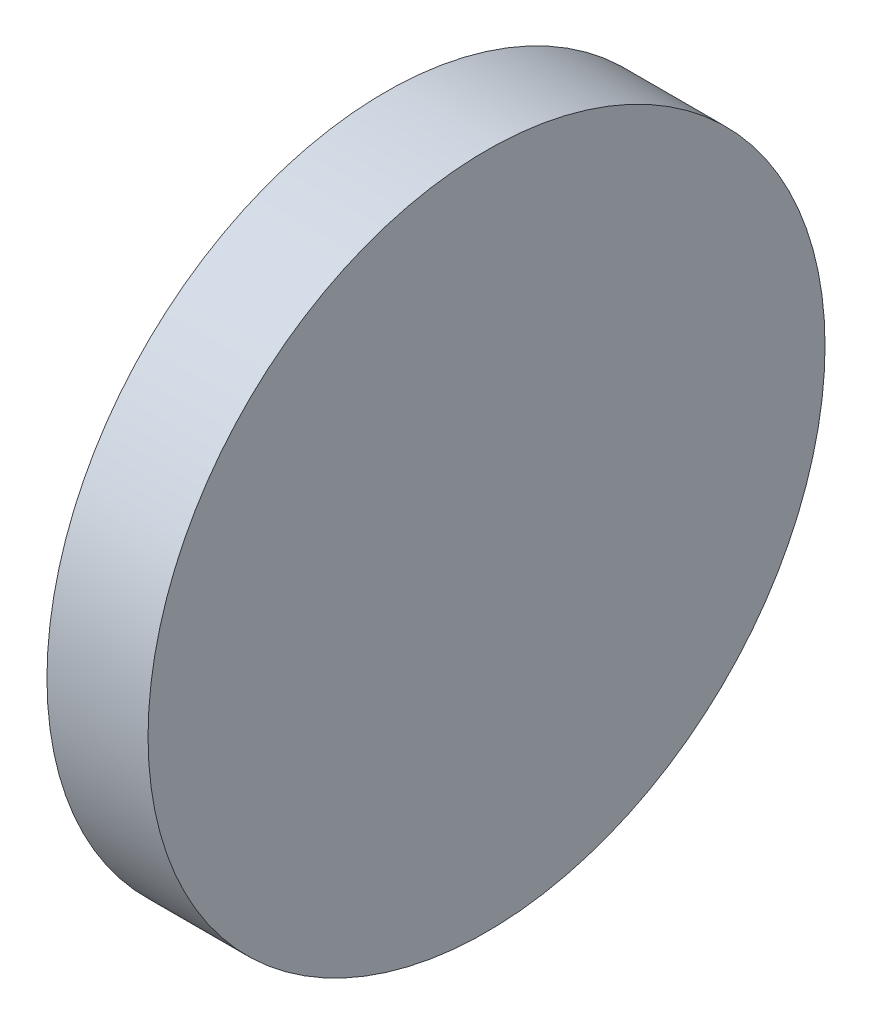
SolidWorks part; units mm, degrees
ref_plane "Front Plane" through (0, 0, 0) normal (0, 0, 1) x (1, 0, 0)
ref_plane "Top Plane" through (0, 0, 0) normal (0, 1, 0) x (1, 0, 0)
ref_plane "Right Plane" through (0, 0, 0) normal (1, 0, 0) x (0, 0, -1)
sketch "Sketch1" plane through (0, 0, 0) normal (0, 0, 1) x (1, 0, 0)
  line L1 (-3.5, 11.7221) -> (3.5, 11.7221)
  line L2 (-3.5, 11.7221) -> (-3.5, -11.7221)
  line L3 (-3.5, -11.7221) -> (3.5, -11.7221)
  line L4 (3.5, 11.7221) -> (3.5, -11.7221)
  line L5 (-3.5, 11.7221) -> (3.5, -11.7221) construction
  line L6 (-3.5, -11.7221) -> (3.5, 11.7221) construction
  point P0 (0, 0)
  dimension "D1" = 7
  dimension "D2" = 23.4442
revolve "Revolve1" add sketch "Sketch1" angle 360 about L3
